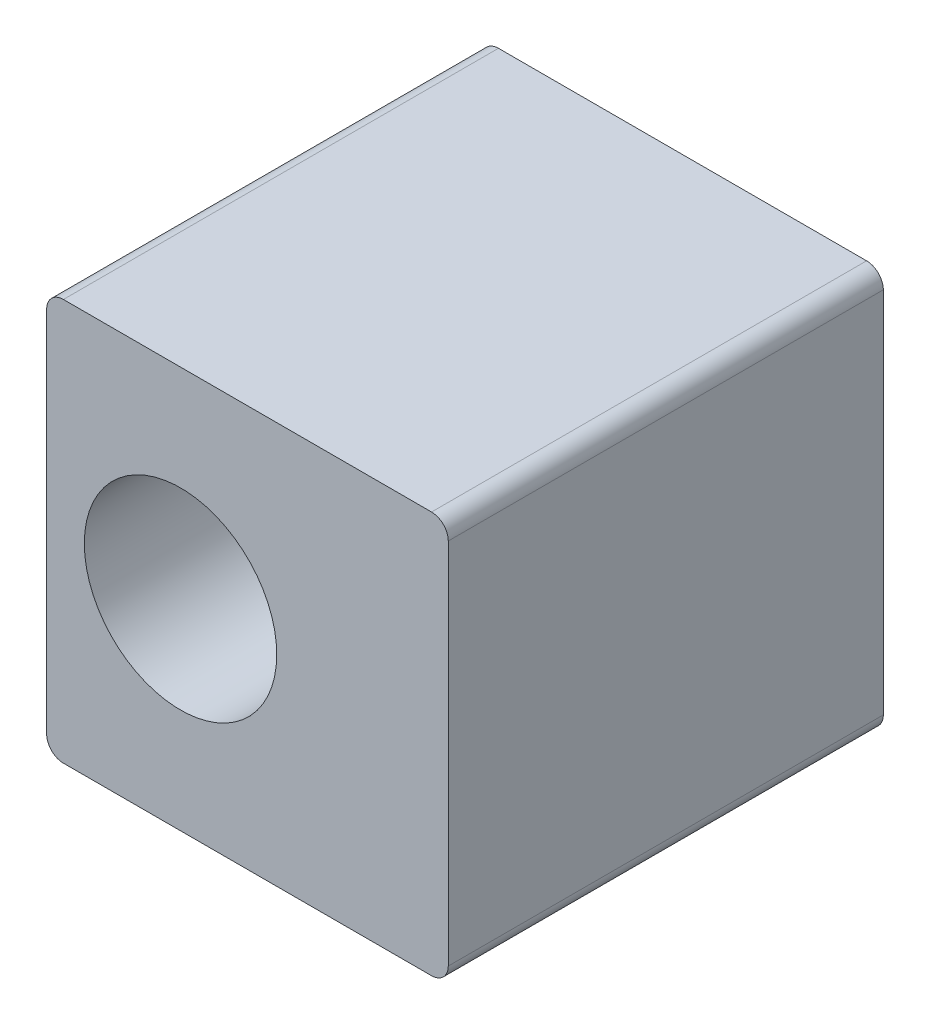
SolidWorks part; units mm, degrees
ref_plane "Front Plane" through (0, 0, 0) normal (0, 0, 1) x (1, 0, 0)
ref_plane "Top Plane" through (0, 0, 0) normal (0, 1, 0) x (1, 0, 0)
ref_plane "Right Plane" through (0, 0, 0) normal (1, 0, 0) x (0, 0, -1)
sketch "Sketch1" plane through (0, 0, 0) normal (0, 0, 1) x (1, 0, 0)
  line L0 (0, 0) -> (-4, 0)
  line L1 (-4, -6) -> (8, -6)
  line L2 (-4, -6) -> (-4, 6)
  line L3 (-4, 6) -> (8, 6)
  line L4 (8, -6) -> (8, 6)
  circle A0 centre (0, 0) radius 4.5
  circle A1 centre (0, 0) radius 2.875
  dimension "D1" = 9
  dimension "D3" = 5.75
  dimension "D2" = 12
  dimension "D4" = 12
  dimension "D5" = 4
extrude "Boss-Extrude1" add sketch "Sketch1" along normal blind 5 contours A1 A0 | L2 A0 L1 L4 L3 region at (-3.8762, 1.0308, 0) region at (1.1007, -4.5381, 0)
extrude "Boss-Extrude3" add sketch "Sketch1<4>" against normal blind 8 contours A0 L2 L1 L4 L3 region at (1.1007, -4.5381, 0)
sketch "Sketch1<4>" plane through (0, 0, 0) normal (0, 0, 1) x (1, 0, 0) same geometry as "Sketch1"
fillet "Fillet1" radius 0.5 6 edges at (-4, 6, -1.5) (8, 6, -1.5) (8, -6, -1.5) (-4, -6, -1.5) (-4, 2.0616, -4) (-4, -2.0616, -4)
sketch "Sketch2" plane through (0, -6, 0) normal (0, -1, 0) x (1, 0, 0)
  line L0 (-3.5, -8) -> (7.5, -8) construction
  line L1 (4.9, -8) -> (6.5, -8)
  line L2 (4.9, -8) -> (4.9, 3.5)
  line L3 (4.9, 3.5) -> (6.5, 3.5)
  line L4 (6.5, -8) -> (6.5, 3.5)
  line L5 (8, 5) -> (8, -8) construction
  line L6 (-3.5, 5) -> (7.5, 5) construction
  dimension "D1" = 1.6
  dimension "D2" = 1.5
  dimension "D3" = 1.5
extrude "Cut-Extrude1" cut sketch "Sketch2" against normal blind 6
sketch "Sketch3" plane through (0, -6, 0) normal (0, -1, 0) x (1, 0, 0)
  line L0 (4.9, -8) -> (5.05, -8)
  line L1 (4.9, -8) -> (6.5, -8) construction
  line L2 (5.05, -6.8) -> (4.9, -6.8)
  line L3 (4.9, 3.5) -> (4.9, -8) construction
  line L4 (5.65, -7.4) -> (5.65, -6.8) construction
  line L5 (4.9, -6.8) -> (4.9, -8)
  line L6 (5.05, -4.8) -> (4.9, -4.8)
  line L7 (4.9, -4.8) -> (4.9, -6)
  line L8 (4.9, -6) -> (5.05, -6)
  line L9 (5.05, -2.8) -> (4.9, -2.8)
  line L10 (4.9, -2.8) -> (4.9, -4)
  line L11 (4.9, -4) -> (5.05, -4)
  line L12 (5.05, -0.8) -> (4.9, -0.8)
  line L13 (4.9, -0.8) -> (4.9, -2)
  line L14 (4.9, -2) -> (5.05, -2)
  line L15 (5.05, 1.2) -> (4.9, 1.2)
  line L16 (4.9, 1.2) -> (4.9, 0)
  line L17 (4.9, 0) -> (5.05, 0)
  line L18 (5.05, 3.2) -> (4.9, 3.2)
  line L19 (4.9, 3.2) -> (4.9, 2)
  line L20 (4.9, 2) -> (5.05, 2)
  line L21 (5.05, -8) -> (5.05, -6) construction
  arc A0 (5.05, -8) -> (5.05, -6.8) centre (5.05, -7.4) ccw
  arc A1 (5.05, -6) -> (5.05, -4.8) centre (5.05, -5.4) ccw
  arc A2 (5.05, -4) -> (5.05, -2.8) centre (5.05, -3.4) ccw
  arc A3 (5.05, -2) -> (5.05, -0.8) centre (5.05, -1.4) ccw
  arc A4 (5.05, 0) -> (5.05, 1.2) centre (5.05, 0.6) ccw
  arc A5 (5.05, 2) -> (5.05, 3.2) centre (5.05, 2.6) ccw
  dimension "D1" = 0.6
  dimension "D2" = 0.75
  dimension "D4" = 2
  dimension "D3" = 6
extrude "Boss-Extrude4" add sketch "Sketch3" against normal up to next
